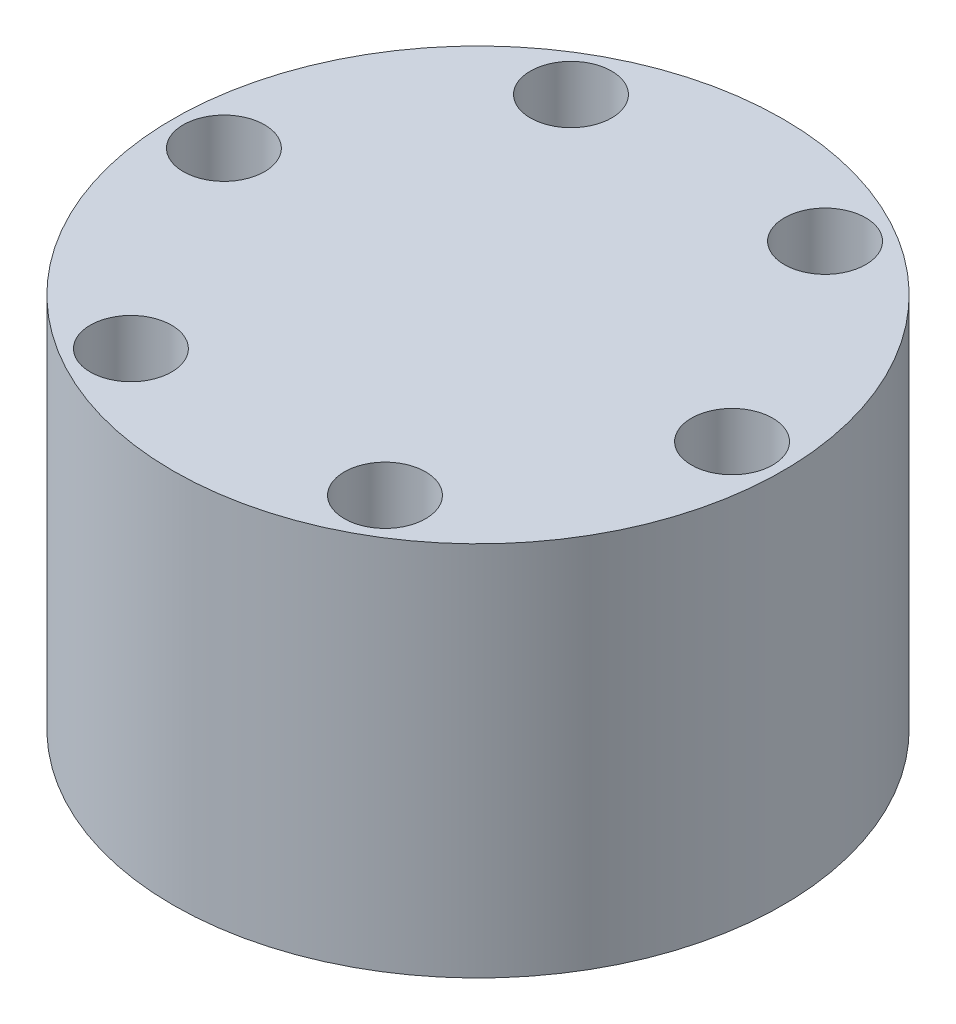
SolidWorks part; units mm, degrees
ref_plane "Front Plane" through (0, 0, 0) normal (0, 0, 1) x (1, 0, 0)
ref_plane "Top Plane" through (0, 0, 0) normal (0, 1, 0) x (1, 0, 0)
ref_plane "Right Plane" through (0, 0, 0) normal (1, 0, 0) x (0, 0, -1)
sketch "Sketch1" plane through (0, 0, 0) normal (0, 1, 0) x (1, 0, 0)
  circle A0 centre (0, 0) radius 15
  circle A1 centre (0, 0) radius 12.5 construction
  circle A2 centre (0, 12.5) radius 1.5
  circle A3 centre (10.8253, 6.25) radius 1.5
  circle A4 centre (10.8253, -6.25) radius 1.5
  circle A5 centre (0, -12.5) radius 1.5
  circle A6 centre (-10.8253, -6.25) radius 1.5
  circle A7 centre (-10.8253, 6.25) radius 1.5
  point P19 (0, 0)
  dimension "D1" = 30
  dimension "D2" = 25
  dimension "D3" = 3
  dimension "D4" = 6
extrude "Boss-Extrude1" add sketch "Sketch1" along normal blind 4
sketch "Sketch2" plane through (0, 4, 0) normal (0, 1, 0) x (1, 0, 0)
  circle A0 centre (0, 0) radius 15
  dimension "D1" = 30
extrude "Boss-Extrude2" add sketch "Sketch2" along normal blind 14.5
sketch "Sketch5" plane through (0, 18.5, 0) normal (0, 1, 0) x (1, 0, 0)
  circle A0 centre (0, 0) radius 12.5 construction
  circle A1 centre (-12.5, 0) radius 2
  circle A2 centre (-6.25, 10.8253) radius 2
  circle A3 centre (6.25, 10.8253) radius 2
  circle A4 centre (12.5, 0) radius 2
  circle A5 centre (6.25, -10.8253) radius 2
  circle A6 centre (-6.25, -10.8253) radius 2
  point P17 (0, 0)
  dimension "D1" = 25
  dimension "D2" = 4
  dimension "D3" = 6
extrude "Cut-Extrude3" cut sketch "Sketch5" against normal blind 6.5
sketch "Sketch6" plane through (0, 0, 0) normal (0, -1, 0) x (1, 0, 0)
  circle A0 centre (0, 0) radius 7.5
  dimension "D1" = 15
extrude "Cut-Extrude4" cut sketch "Sketch6" against normal blind 5
